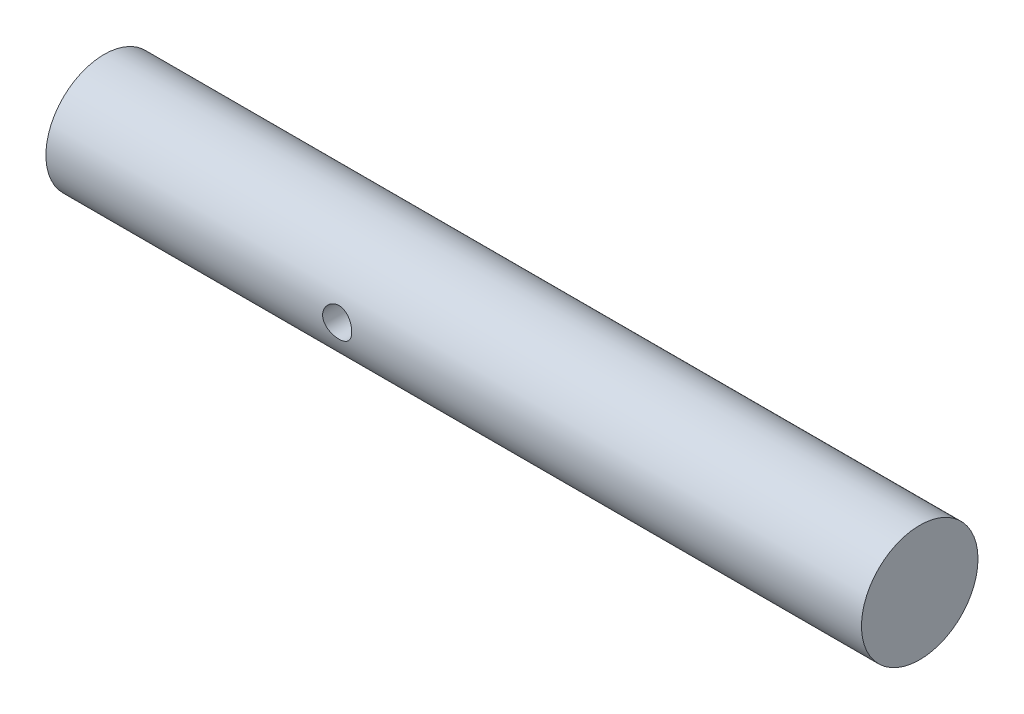
SolidWorks part; units mm, degrees
ref_plane "Front Plane" through (0, 0, 0) normal (0, 0, 1) x (1, 0, 0)
ref_plane "Top Plane" through (0, 0, 0) normal (0, 1, 0) x (1, 0, 0)
ref_plane "Right Plane" through (0, 0, 0) normal (1, 0, 0) x (0, 0, -1)
sketch "Sketch1" plane through (0, 0, 0) normal (0, 0, 1) x (1, 0, 0)
  line L0 (0, 0) -> (177.8, 0)
  point P3 (139.7, 0)
  dimension "D1" = 177.8
  dimension "D2" = 38.1
sweep "Sweep1" add path "Sketch1" circular profile diameter 25.4 parameters "D3"=25.4
sketch "Sketch18" plane through (0, 0, 0) normal (0, 0, 1) x (1, 0, 0)
  circle A0 centre (139.7, 0) radius 3.175
  dimension "D1" = 6.35
extrude "Cut-Extrude1" cut sketch "Sketch18" against normal through all
pattern_linear "LPattern1" count 4 spacing 25.4 along (-1, 0, 0) of "Cut-Extrude1"
sketch "Sketch19" plane through (0, 0, 0) normal (0, 0, -1) x (-1, 0, 0)
  circle A1 centre (-63.5, 0) radius 3.175
  circle A2 centre (-63.5, 0) radius 3.175
  dimension "D1" = 0
extrude "Cut-Extrude2" cut sketch "Sketch19" against normal through all
equation "\"bar_dia\"= 1in"
equation "\"hole_dia\"= 0.25in"
equation "\"D3@Sweep1\"=\"bar_dia\""
equation "\"D1@Sketch18\"=\"hole_dia\""
